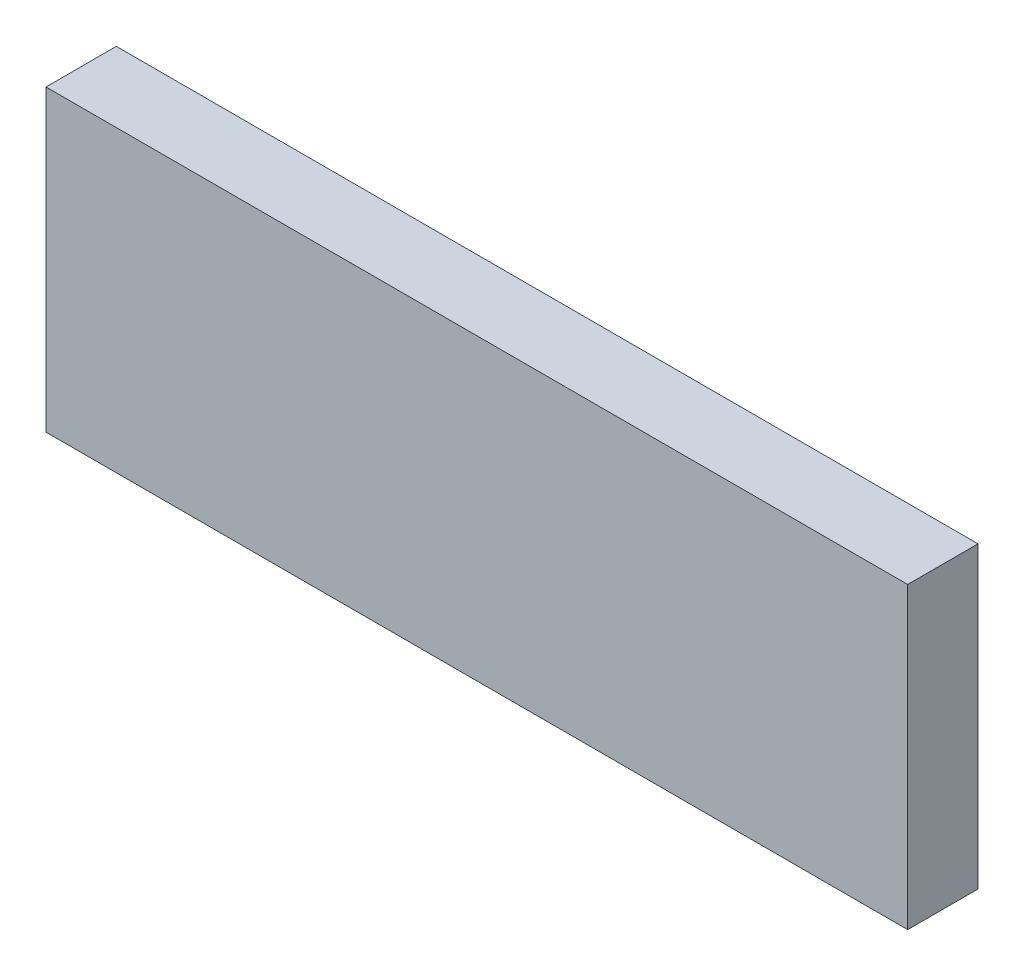
SolidWorks part; units mm, degrees
ref_plane "Front" through (0, 0, 0) normal (0, 0, 1) x (1, 0, 0)
ref_plane "Top" through (0, 0, 0) normal (0, 1, 0) x (1, 0, 0)
ref_plane "Right" through (0, 0, 0) normal (1, 0, 0) x (0, 0, -1)
sketch "Sketch1" plane through (0, 0, 0) normal (0, 1, 0) x (1, 0, 0)
  line L1 (-155.575, -12.7) -> (155.575, -12.7)
  line L2 (-155.575, -12.7) -> (-155.575, 12.7)
  line L3 (-155.575, 12.7) -> (155.575, 12.7)
  line L4 (155.575, -12.7) -> (155.575, 12.7)
  line L5 (-155.575, -12.7) -> (155.575, 12.7) construction
  line L6 (-155.575, 12.7) -> (155.575, -12.7) construction
  point P0 (0, 0)
  dimension "D1" = 25.4
  dimension "D2" = 311.15
extrude "Boss-Extrude1" add sketch "Sketch1" along normal mid plane 107.95
